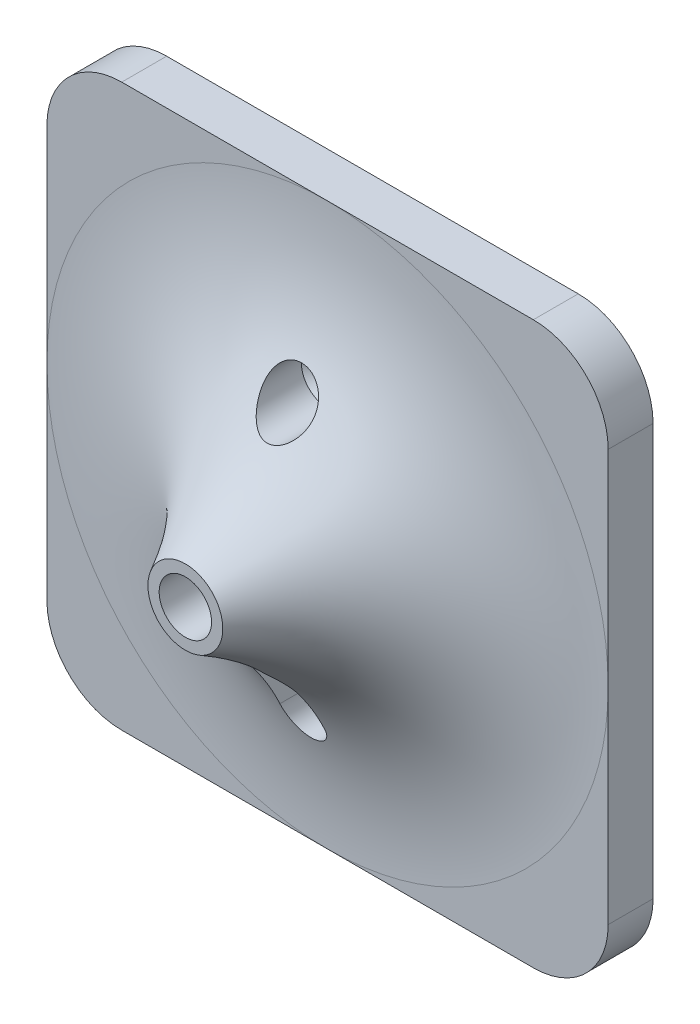
SolidWorks part; units mm, degrees
ref_plane "Front Plane" through (0, 0, 0) normal (0, 0, 1) x (1, 0, 0)
ref_plane "Top Plane" through (0, 0, 0) normal (0, 1, 0) x (1, 0, 0)
ref_plane "Right Plane" through (0, 0, 0) normal (1, 0, 0) x (0, 0, -1)
sketch "Sketch1" plane through (0, 0, 0) normal (0, 0, 1) x (1, 0, 0)
  line L1 (-27.5, 37.5) -> (27.5, 37.5)
  line L2 (-37.5, 27.5) -> (-37.5, -27.5)
  line L3 (-27.5, -37.5) -> (27.5, -37.5)
  line L4 (37.5, 27.5) -> (37.5, -27.5)
  line L5 (-37.5, 37.5) -> (37.5, -37.5) construction
  line L6 (-37.5, -37.5) -> (37.5, 37.5) construction
  arc A0 (-37.5, -27.5) -> (-27.5, -37.5) centre (-27.5, -27.5) ccw
  arc A1 (27.5, -37.5) -> (37.5, -27.5) centre (27.5, -27.5) ccw
  arc A2 (27.5, 37.5) -> (37.5, 27.5) centre (27.5, 27.5) cw
  arc A3 (-27.5, 37.5) -> (-37.5, 27.5) centre (-27.5, 27.5) ccw
  point P0 (0, 0)
  dimension "D3" = 10
  dimension "D1" = 75
  dimension "D2" = 75
extrude "Boss-Extrude1" add sketch "Sketch1" along normal blind 25
sketch "Sketch5" plane through (0, 0, 25) normal (0, 0, 1) x (1, 0, 0)
  circle A0 centre (0, 0) radius 3.5
  dimension "D1" = 7
extrude "Cut-Extrude1" cut sketch "Sketch5" against normal blind 15
sketch "Sketch6" plane through (0, 0, 10) normal (0, 0, 1) x (1, 0, 0)
  circle A0 centre (0, 0) radius 2.5
  dimension "D1" = 5
extrude "Cut-Extrude2" cut sketch "Sketch6" against normal through all
sketch "Sketch7" plane through (0, 0, 0) normal (0, 0, -1) x (-1, 0, 0)
  line L1 (0, -5.1962) -> (4.5, -2.5981)
  line L2 (4.5, -2.5981) -> (4.5, 2.5981)
  line L3 (4.5, 2.5981) -> (0, 5.1962)
  line L4 (0, 5.1962) -> (-4.5, 2.5981)
  line L5 (-4.5, 2.5981) -> (-4.5, -2.5981)
  line L6 (-4.5, -2.5981) -> (0, -5.1962)
  circle A0 centre (0, 0) radius 4.5 construction
  point P1 (0, 0)
  dimension "D1" = 9
extrude "Cut-Extrude3" cut sketch "Sketch7" against normal blind 4
sketch "Sketch3" plane through (0, -37.5, 0) normal (0, -1, 0) x (1, 0, 0)
  line L4 (2, 2) -> (2, 0)
  line L5 (41.25, 0) -> (-41.25, 0) construction
  line L6 (2, 0) -> (-2, 0)
  line L7 (-2, 0) -> (-2, 2)
  arc A1 (2, 2) -> (-2, 2) centre (0, 2) ccw
  dimension "D1" = 4
extrude "Cut-Extrude4" cut sketch "Sketch3" against normal blind 20
sketch "Sketch10" plane through (0, 0, 25) normal (0, 0, 1) x (1, 0, 0)
  circle A0 centre (0, 17) radius 3.5
  circle A2 centre (0, 0) radius 3.5 construction
  point P4 (0, 0)
  dimension "D1" = 7
  dimension "D2" = 10
sketch "Sketch8" plane through (0, 0, 0) normal (0, 1, 0) x (1, 0, 0)
  line L0 (0, 0) -> (0, -50000) construction
  line L1 (37.5, -25) -> (37.5, 0) construction
  line L2 (27.5, -25) -> (-27.5, -25) construction
  line L3 (5, -25) -> (5, -35)
  line L4 (5, -35) -> (67.5, -35)
  line L5 (67.5, -35) -> (67.5, -6)
  line L6 (67.5, -6) -> (37.5, -6)
  line L7 (-41.25, 0) -> (41.25, 0) construction
  spline S0 degree 2 poles (37.5, -6) (15.2106, -5.8474) (5, -25) knots 0 0 0 1 1 1
  point P5 (17.1993, -10.7623)
  point P16 (16.6454, -11.6654)
  dimension "D1" = 30
  dimension "D2" = 10
  dimension "D3" = 5
  dimension "D4" = 6
revolve "Cut-Revolve2" cut sketch "Sketch8" angle 360 about L0
sketch "Sketch9" plane through (0, 0, 0) normal (0, 0, -1) x (-1, 0, 0)
  line L1 (0, -14.5) -> (0, -20.5) construction
  line L2 (3, -14.5) -> (3, -20.5)
  line L3 (-3, -14.5) -> (-3, -20.5)
  line L4 (-2, -17.5) -> (2, -17.5) construction
  arc A1 (3, -14.5) -> (-3, -14.5) centre (0, -14.5) ccw
  arc A2 (-3, -20.5) -> (3, -20.5) centre (0, -20.5) ccw
  point P2 (0, -17.5)
  point P8 (0, -16.6051)
  point P9 (0, -17.5)
  dimension "D1" = 6
  dimension "D2" = 3
extrude "Cut-Extrude6" cut sketch "Sketch9" against normal up to next
extrude "Cut-Extrude7" cut sketch "Sketch10" against normal blind 20
sketch "Sketch11" plane through (0, 0, 5) normal (0, 0, 1) x (1, 0, 0)
  circle A0 centre (0, 17) radius 3.5 construction
  circle A1 centre (0, 17) radius 3.5 construction
  circle A2 centre (0, 17) radius 2.25
  dimension "D1" = 4.5
extrude "Cut-Extrude8" cut sketch "Sketch11" against normal through all
chamfer "Chamfer1" distance 1 angle 45 8 edges at (3.5, 17, 5) (-2.5, 0, 4) (4.5, 0, 4) (2.25, 3.8971, 4) (-2.25, 3.8971, 4) (-4.5, 0, 4) (-2.25, -3.8971, 4) (2.25, -3.8971, 4)
fillet "Fillet1" radius 2 3 edges at (-2, -22.7361, 1) (-0.0378, -23.4998, 3.9996) (2, -22.7361, 1)
